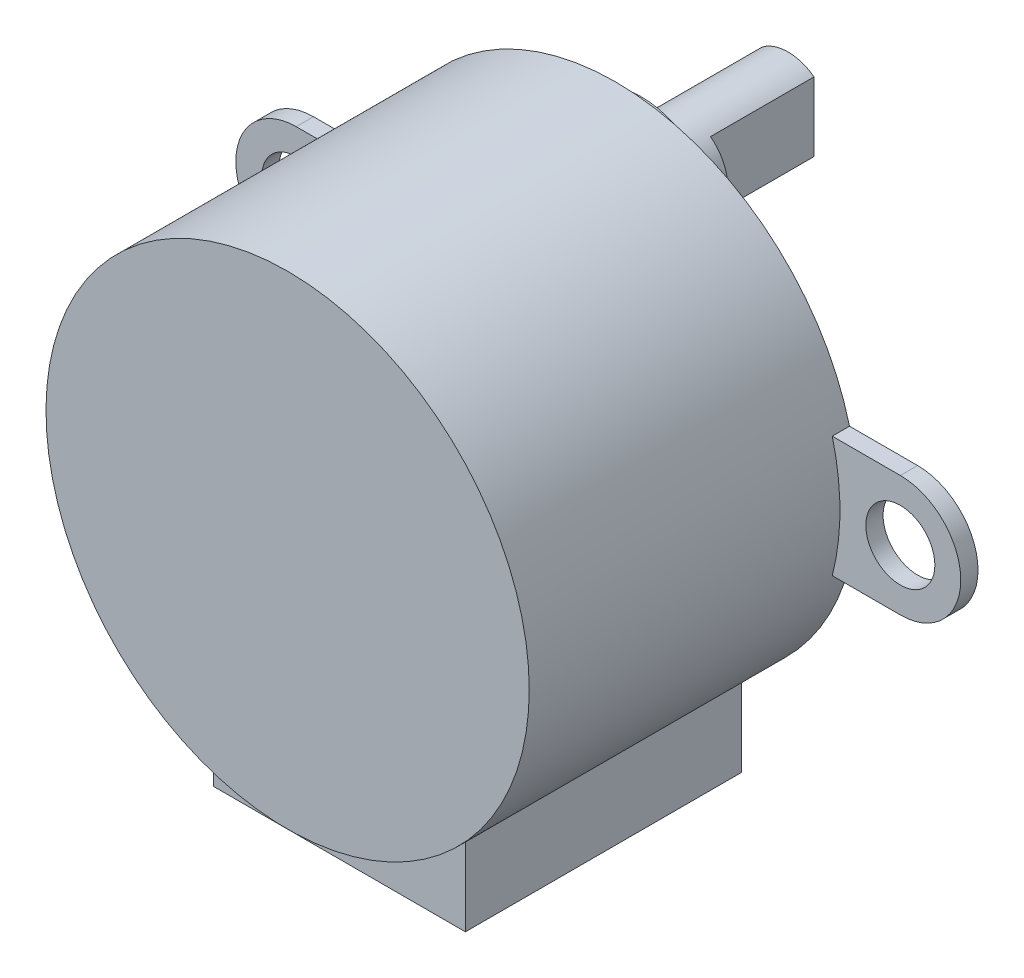
SolidWorks part; units mm, degrees
ref_plane "Face" through (0, 0, 0) normal (0, 0, 1) x (1, 0, 0)
ref_plane "Dessus" through (0, 0, 0) normal (0, 1, 0) x (1, 0, 0)
ref_plane "Droite" through (0, 0, 0) normal (1, 0, 0) x (0, 0, -1)
sketch "Esquisse1" plane through (0, 0, 0) normal (0, 0, 1) x (1, 0, 0)
  line L0 (-17.5, 0) -> (17.5, 0) construction
  line L1 (0, 0) -> (0, 8) construction
  line L2 (-7.3, -17) -> (7.3, -17)
  line L3 (-7.3, -17) -> (-7.3, -11.9461)
  line L4 (7.3, -17) -> (7.3, -11.9461)
  line L5 (-17.5, 3.5) -> (-13.5554, 3.5)
  line L6 (-17.5, -3.5) -> (-13.5554, -3.5)
  line L7 (17.5, -3.5) -> (13.5554, -3.5)
  line L8 (17.5, 3.5) -> (13.5554, 3.5)
  circle A0 centre (0, 0) radius 14 construction
  circle A1 centre (-17.5, 0) radius 2
  circle A2 centre (17.5, 0) radius 2
  circle A3 centre (0, 8) radius 2.5
  circle A4 centre (0, 8) radius 1.5
  circle A5 centre (0, 8) radius 4.5
  arc A6 (-17.5, -3.5) -> (-17.5, 3.5) centre (-17.5, 0) cw
  arc A7 (17.5, -3.5) -> (17.5, 3.5) centre (17.5, 0) ccw
  circle A8 centre (0, 0) radius 14
  point P5 (0, 0)
  point P14 (0, -17)
  dimension "D1" = 28
  dimension "D3" = 4
  dimension "D5" = 9
  dimension "D6" = 5
  dimension "D7" = 3
  dimension "D10" = 3.5
  dimension "D2" = 35
  dimension "D4" = 8
  dimension "D8" = 17
  dimension "D9" = 14.6
extrude "Boss.-Extru.1" add sketch "Esquisse1" along normal blind 1 contours L4 L7 A7 L8 L5 A6 L6 L3 L2 A1 A2 A5 | A5 A3 | A4 | A3 A4 | A8 L5 A6 L6 A1 | A8 L7 A7 L8 A2 | A8 L3 L2 L4 region at (0, -15.1184, 0) region at (0, -0.9218, 0) region at (-15.5277, -3.3978, 0) region at (13.9898, -1.7769, 0) region at (-2.4293, 8, 0) region at (0, 8, 0) region at (-4.3727, 8, 0)
extrude "Boss.-Extru.2" add sketch "Esquisse1<3>" along normal blind 19 contours A8 A5 | A5 A3 | A3 A4 | A4 region at (0, -0.9218, 0) region at (-2.4293, 8, 0) region at (0, 8, 0) region at (-4.3727, 8, 0)
sketch "Esquisse1<3>" plane through (0, 0, 0) normal (0, 0, 1) x (1, 0, 0) same geometry as "Esquisse1"
extrude "Boss.-Extru.3" add sketch "Esquisse1<4>" along normal blind 16 contours A8 L3 L2 L4 region at (0, -15.1184, 0)
sketch "Esquisse1<4>" plane through (0, 0, 0) normal (0, 0, 1) x (1, 0, 0) same geometry as "Esquisse1"
extrude "Boss.-Extru.4" add sketch "Esquisse1<5>" against normal blind 1.5 contours A5
sketch "Esquisse1<5>" plane through (0, 0, 0) normal (0, 0, 1) x (1, 0, 0) same geometry as "Esquisse1"
extrude "Boss.-Extru.5" add sketch "Esquisse1<6>" against normal blind 10 contours A3
sketch "Esquisse1<6>" plane through (0, 0, 0) normal (0, 0, 1) x (1, 0, 0) same geometry as "Esquisse1"
sketch "Esquisse2" plane through (0, 0, -10) normal (0, 0, -1) x (-1, 0, 0)
  line L0 (0, 10.5) -> (0, 5.5) construction
  line L1 (2.5, 10.5) -> (2.5, 5.5)
  line L2 (-2.5, 10.5) -> (-1.5, 10.5)
  line L3 (-2.5, 10.5) -> (-2.5, 5.5)
  line L4 (-2.5, 5.5) -> (-1.5, 5.5)
  line L5 (-1.5, 10.5) -> (-1.5, 5.5)
  line L6 (2.5, 5.5) -> (1.5, 5.5)
  line L7 (1.5, 10.5) -> (1.5, 5.5)
  line L8 (2.5, 10.5) -> (1.5, 10.5)
  circle A0 centre (0, 8) radius 2.5 construction
  circle A1 centre (0, 8) radius 2.5 construction
  dimension "D1" = 1.5
extrude "Enlèv. mat.-Extru.1" cut sketch "Esquisse2" against normal blind 6
